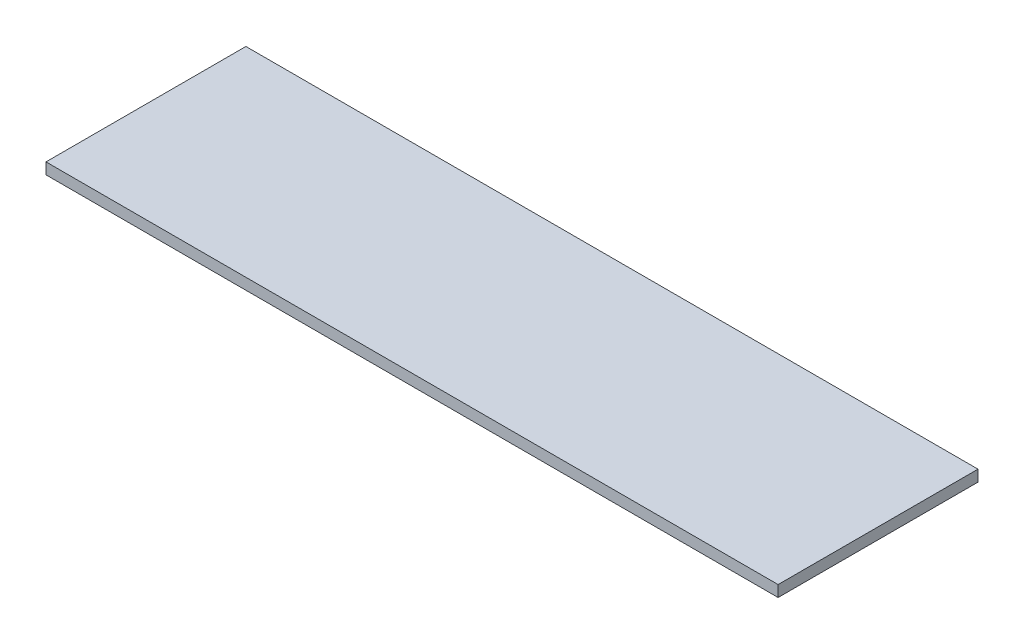
SolidWorks part; units mm, degrees
ref_plane "Front Plane" through (0, 0, 0) normal (0, 0, 1) x (1, 0, 0)
ref_plane "Top Plane" through (0, 0, 0) normal (0, 1, 0) x (1, 0, 0)
ref_plane "Right Plane" through (0, 0, 0) normal (1, 0, 0) x (0, 0, -1)
sketch "Sketch1" plane through (0, 0, 0) normal (0, 1, 0) x (1, 0, 0)
  line L1 (146.5, -40) -> (-146.5, -40)
  line L2 (146.5, -40) -> (146.5, 40)
  line L3 (146.5, 40) -> (-146.5, 40)
  line L4 (-146.5, -40) -> (-146.5, 40)
  line L5 (146.5, -40) -> (-146.5, 40) construction
  line L6 (146.5, 40) -> (-146.5, -40) construction
  point P0 (0, 0)
  dimension "D1" = 293
  dimension "D2" = 80
extrude "Boss-Extrude1" add sketch "Sketch1" along normal blind 4.5
